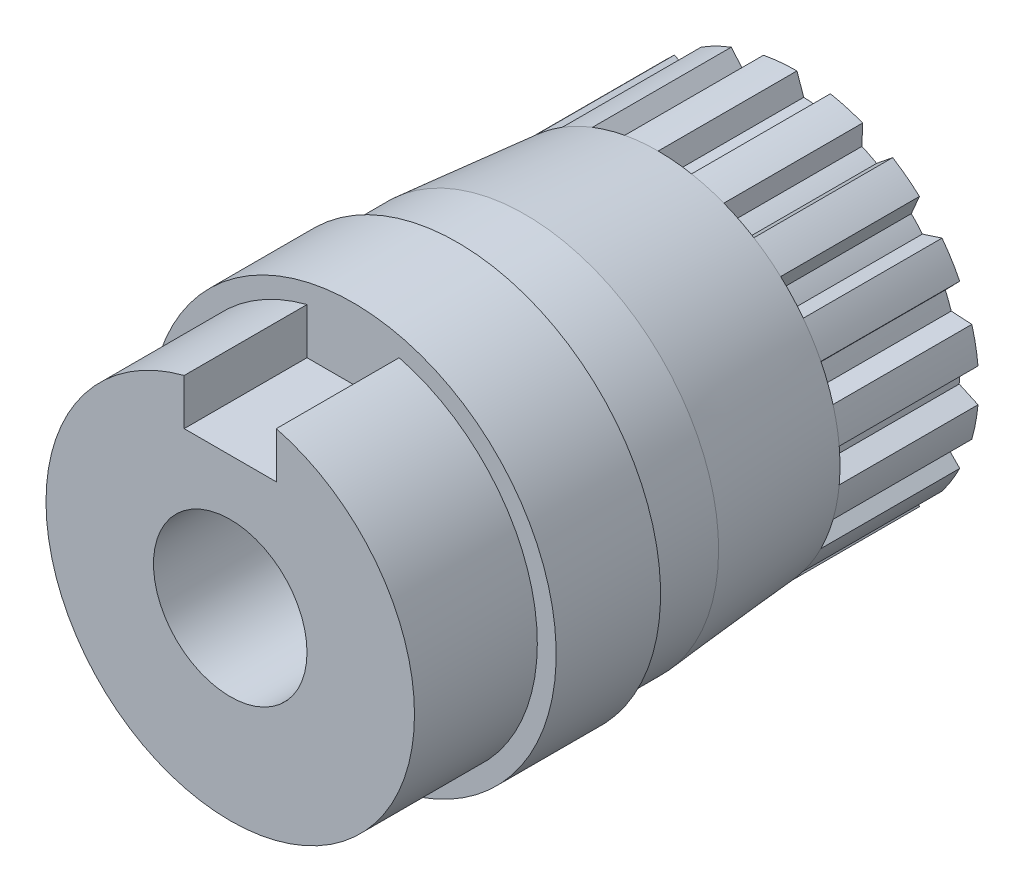
SolidWorks part; units mm, degrees
material "AISI 1045 Steel, cold drawn"
ref_plane "Front Plane" through (0, 0, 0) normal (0, 0, 1) x (1, 0, 0)
ref_plane "Top Plane" through (0, 0, 0) normal (0, 1, 0) x (1, 0, 0)
ref_plane "Right Plane" through (0, 0, 0) normal (1, 0, 0) x (0, 0, -1)
sketch "Sketch2" plane through (0, 0, 0) normal (0, 1, 0) x (1, 0, 0)
  line L0 (-18.8, -6.1135) -> (-18.8, -31.0462) construction
  line L1 (0, -14.35) -> (0, -58.5938)
  line L2 (0, -58.5938) -> (-19.05, -58.5938)
  line L3 (-21, -45.8938) -> (-21, -35.1)
  line L5 (-21, -35.1) -> (-21, -28.1) construction
  line L6 (12.2546, -28.1) -> (-27.0228, -28.1) construction
  line L7 (-27.0228, -14.35) -> (10.6457, -14.35) construction
  line L8 (-21, -35.1) -> (-20, -35.1)
  line L9 (-20, -28.1) -> (-20, -35.1)
  line L10 (-20, -28.1) -> (-18.8, -14.35)
  line L11 (-18.8, -14.35) -> (0, -14.35)
  line L12 (-21, -45.8938) -> (-19.05, -45.8938)
  line L13 (-19.05, -45.8938) -> (-19.05, -58.5938)
  dimension "D1" = 14.35
  dimension "D4" = 18.8
  dimension "D8" = 19.05
  dimension "D2" = 21
  dimension "D3" = 10.7938
  dimension "D5" = 28.1
  dimension "D6" = 7
  dimension "D7" = 20
  dimension "D9" = 12.7
revolve "Revolve1" add sketch "Sketch2" angle 360 about L1
sketch "Sketch4" plane through (0, 0, 0) normal (0, 0, 1) x (1, 0, 0)
  line L0 (0, 18.8) -> (0, 0) construction
  line L1 (0, 0) -> (-3.4545, 18.4799) construction
  line L2 (0, 0) -> (-6.7913, 17.5305) construction
  line L3 (-3.4545, 18.4799) -> (-3.7741, 16.3706)
  line L4 (-5.4092, 15.9054) -> (-6.7913, 17.5305)
  line L5 (0, 18.8) -> (0, 0)
  line L6 (0, 0) -> (-6.7913, 17.5305)
  circle A0 centre (0, 0) radius 18.8 construction
  circle A1 centre (0, 0) radius 16.8 construction
  arc A2 (0, 18.8) -> (-3.4545, 18.4799) centre (0, 0) ccw
  arc A3 (-3.4545, 18.4799) -> (-6.7913, 17.5305) centre (0, 0) ccw construction
  arc A4 (-3.7741, 16.3706) -> (-5.4092, 15.9054) centre (0, 0) ccw
  dimension "D1" = 37.6
  dimension "D3" = 10.588
  dimension "D4" = 10.588
  dimension "D5" = 1.7
  dimension "D2" = 2
extrude "Boss-Extrude1" add sketch "Sketch4" along normal blind 27.94
pattern_circular "CirPattern1" count 17 over 360 about axis through (0, 0, 27.94) along (0, 0, -1) of "Boss-Extrude1" reverse direction yes
sketch "Sketch5" plane through (0, 0, 58.5938) normal (0, 0, 1) x (1, 0, 0)
  line L0 (0, 0) -> (0, 19.05) construction
  line L1 (-4.7625, 25.2589) -> (4.7625, 25.2589)
  line L2 (-4.7625, 25.2589) -> (-4.7625, 13.6826)
  line L3 (-4.7625, 13.6826) -> (4.7625, 13.6826)
  line L4 (4.7625, 25.2589) -> (4.7625, 13.6826)
  line L5 (4.7625, 18.4451) -> (-4.7625, 18.4451) construction
  circle A0 centre (0, 0) radius 7.9375
  circle A1 centre (0, 0) radius 19.05 construction
  dimension "D3" = 15.875
  dimension "D1" = 9.525
  dimension "D2" = 4.7625
extrude "Cut-Extrude1" cut sketch "Sketch5" against normal blind 12.7
extrude "Cut-Extrude2" cut sketch "Sketch5<2>" against normal blind 70 contours A0 region at (0, 0, 58.5938)
sketch "Sketch5<2>" plane through (0, 0, 58.5938) normal (0, 0, 1) x (1, 0, 0) same geometry as "Sketch5"
